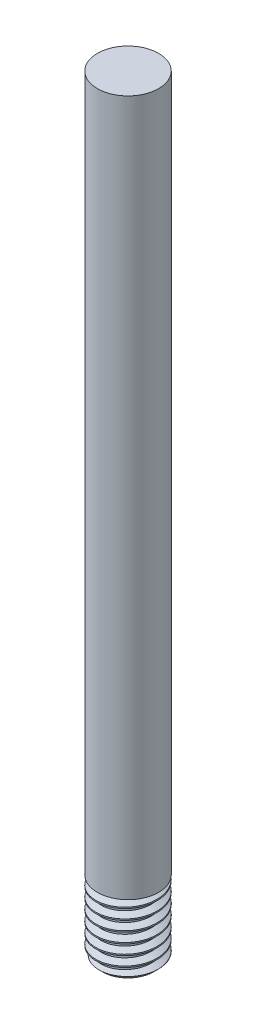
SolidWorks part; units mm, degrees
note: The reader was unsure of these and kept them because the rebuilt part matched: shared geometry of "Sketch1<3>".
ref_plane "Ön Düzlem" through (0, 0, 0) normal (0, 0, 1) x (1, 0, 0)
ref_plane "Üst Düzlem" through (0, 0, 0) normal (0, 1, 0) x (1, 0, 0)
ref_plane "Sağ Düzlem" through (0, 0, 0) normal (1, 0, 0) x (0, 0, -1)
sketch "Sketch1" plane through (0, 0, 0) normal (0, 0, 1) x (1, 0, 0)
  line L0 (-7.5, 80.875) -> (7.5, 80.875)
  line L1 (7.5, -87.875) -> (-7.5, -87.875)
  line L2 (7.5, -87.875) -> (7.5, 87.875)
  line L3 (7.5, 87.875) -> (-7.5, 87.875)
  line L4 (-7.5, -87.875) -> (-7.5, 87.875)
  line L5 (7.5, -87.875) -> (-7.5, 87.875) construction
  line L6 (7.5, 87.875) -> (-7.5, -87.875) construction
  line L7 (-7.5, 87.875) -> (-7.5, 80.875)
  line L8 (-7.5, -14.125) -> (7.5, -14.125)
  line L9 (-3, 80.875) -> (3, 80.875)
  line L10 (-3, 80.875) -> (-3, 87.875)
  line L11 (-3, 87.875) -> (3, 87.875)
  line L12 (3, 80.875) -> (3, 87.875)
  line L13 (-3, 80.875) -> (3, 87.875) construction
  line L14 (-3, 87.875) -> (3, 80.875) construction
  line L15 (-7.5, -87.875) -> (-7.5, -14.125)
  line L16 (0, 111.54) -> (0, -104.9562)
  line L17 (-3, -87.875) -> (3, -87.875)
  line L18 (-3, -87.875) -> (-3, -12.625)
  line L19 (-3, -12.625) -> (3, -12.625)
  line L20 (3, -87.875) -> (3, -12.625)
  line L21 (-5.7474, 80.875) -> (-5.5, 78.875)
  line L22 (5.5, 78.875) -> (-5.5, 78.875)
  line L24 (5.7474, 80.875) -> (-5.7474, 80.875)
  line L26 (5.5052, 78.9171) -> (-5.7474, 80.875) construction
  line L27 (5.7474, 80.875) -> (-5.5052, 78.9171) construction
  line L28 (5.7474, 80.875) -> (5.5, 78.875)
  line L29 (-7.5, 78.875) -> (7.5, 78.875)
  line L30 (-3, -80.875) -> (3, -80.875)
  line L31 (3, -12.625) -> (-3, -12.625)
  line L32 (3, -12.625) -> (3, 55.375)
  line L33 (3, 55.375) -> (-3, 55.375)
  line L34 (-3, -12.625) -> (-3, 55.375)
  line L35 (3, -12.625) -> (-3, 55.375) construction
  line L36 (3, 55.375) -> (-3, -12.625) construction
  point P0 (0, 0)
  point P8 (0, 84.375)
  point P16 (0, 80.875)
  point P22 (0, 79.875)
  point P31 (0, 21.375)
  dimension "D1" = 175.75
  dimension "D2" = 15
  dimension "D3" = 7
  dimension "D4" = 6
  dimension "D5" = 95
  dimension "D6" = 6
  dimension "D7" = 1.5
  dimension "D8" = 68
  dimension "D9" = 5.5
  dimension "D10" = 7
revolve "Revolve1" add sketch "Sketch1" angle 360 about L16
revolve "Revolve2" add sketch "Sketch1<3>" angle 360 about L16
sketch "Sketch1<3>" plane through (0, 0, 0) normal (0, 0, 1) x (1, 0, 0) same geometry as "Sketch1"
chamfer "Chamfer1" distance 0.5 angle 45 1 edges at (0, -87.875, 3)
thread "Thread1" pitch 1 start angle 0, offset 1, length 0, pitch 1, diameter 6
ref_plane "Plane2" through (3, -88.375, 0) normal (0, 0, 1) x (1, 0, 0)
sketch "Thread Profile2" plane through (3, -88.375, 0) normal (0, 0, 1) x (1, 0, 0)
  line L0 (0, 0) -> (0, 1) construction
  line L11 (0, 0) -> (0, 0.875)
  line L12 (0, 0.875) -> (-0.5413, 0.5625)
  line L13 (-0.5413, 0.5625) -> (-0.5413, 0.3125)
  line L15 (-0.5413, 0.3125) -> (0, 0)
  line L17 (-0.5413, 0.4375) -> (0, 0.4375) construction
  point P2 (0, 0)
  dimension "Pitch" = 1
  dimension "Profile_Angle" = 60
  dimension "Profile_Land" = 0.25
  dimension "Profile_Height" = 0.5413
